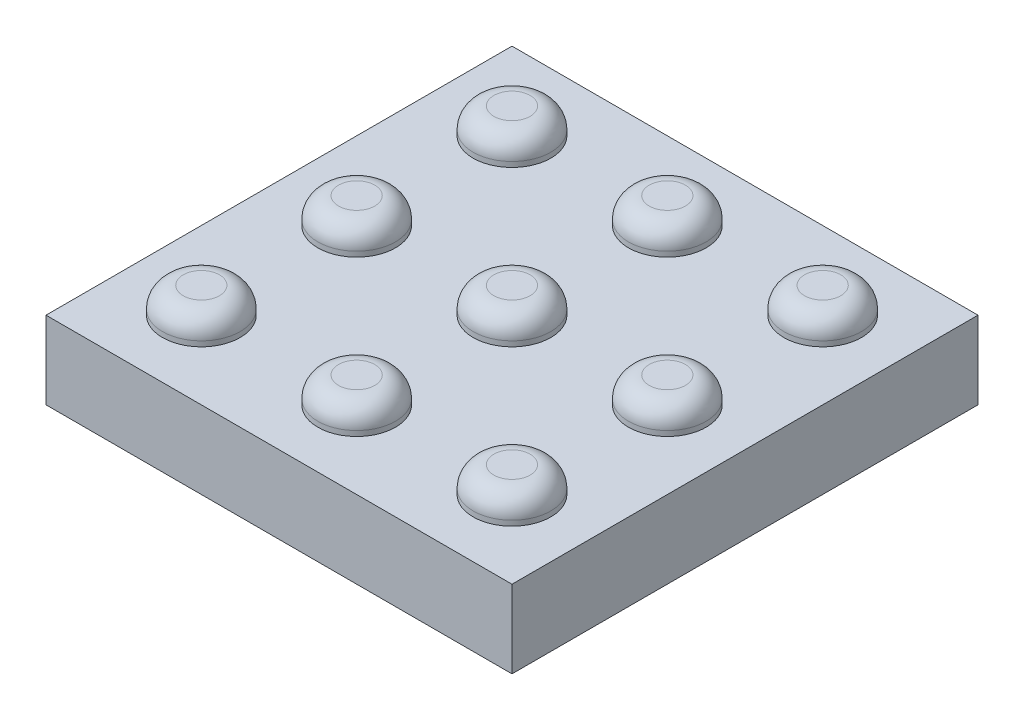
SolidWorks part; units mm, degrees
ref_plane "Front Plane" through (0, 0, 0) normal (0, 0, 1) x (1, 0, 0)
ref_plane "Top Plane" through (0, 0, 0) normal (0, 1, 0) x (1, 0, 0)
ref_plane "Right Plane" through (0, 0, 0) normal (1, 0, 0) x (0, 0, -1)
sketch "Sketch1" plane through (0, 0, 0) normal (0, 1, 0) x (1, 0, 0)
  line L1 (-38.1, -190.5) -> (190.5, -190.5)
  line L2 (-38.1, -190.5) -> (-38.1, 38.1)
  line L3 (-38.1, 38.1) -> (190.5, 38.1)
  line L4 (190.5, -190.5) -> (190.5, 38.1)
  line L5 (-38.1, -190.5) -> (190.5, 38.1) construction
  line L6 (-38.1, 38.1) -> (190.5, -190.5) construction
  circle A0 centre (0, 0) radius 19.05
  circle A1 centre (76.2, 0) radius 19.05
  circle A2 centre (152.4, 0) radius 19.05
  circle A3 centre (0, -76.2) radius 19.05
  circle A4 centre (76.2, -76.2) radius 19.05
  circle A5 centre (152.4, -76.2) radius 19.05
  circle A6 centre (0, -152.4) radius 19.05
  circle A7 centre (76.2, -152.4) radius 19.05
  circle A8 centre (152.4, -152.4) radius 19.05
  dimension "D1" = 38.1
  dimension "D6" = 38.1
  dimension "D7" = 38.1
  dimension "D4" = 76.2
  dimension "D5" = 76.2
  dimension "D2" = 3
  dimension "D3" = 3
extrude "Boss-Extrude1" add sketch "Sketch1" against normal blind 38.1 contours L2 L3 L4 L1
extrude "Boss-Extrude2" add sketch "Sketch1<3>" along normal blind 12.7 contours A4 | A5 | A2 | A1 | A0 | A3 | A6 | A7 | A8
sketch "Sketch1<3>" plane through (0, 0, 0) normal (0, 1, 0) x (1, 0, 0) same geometry as "Sketch1"
fillet "Fillet1" radius 10.16 9 edges at (152.4, 12.7, 19.05) (152.4, 12.7, 95.25) (152.4, 12.7, 171.45) (76.2, 12.7, 171.45) (76.2, 12.7, 95.25) (76.2, 12.7, 19.05) (0, 12.7, 19.05) (0, 12.7, 95.25) (0, 12.7, 171.45)
